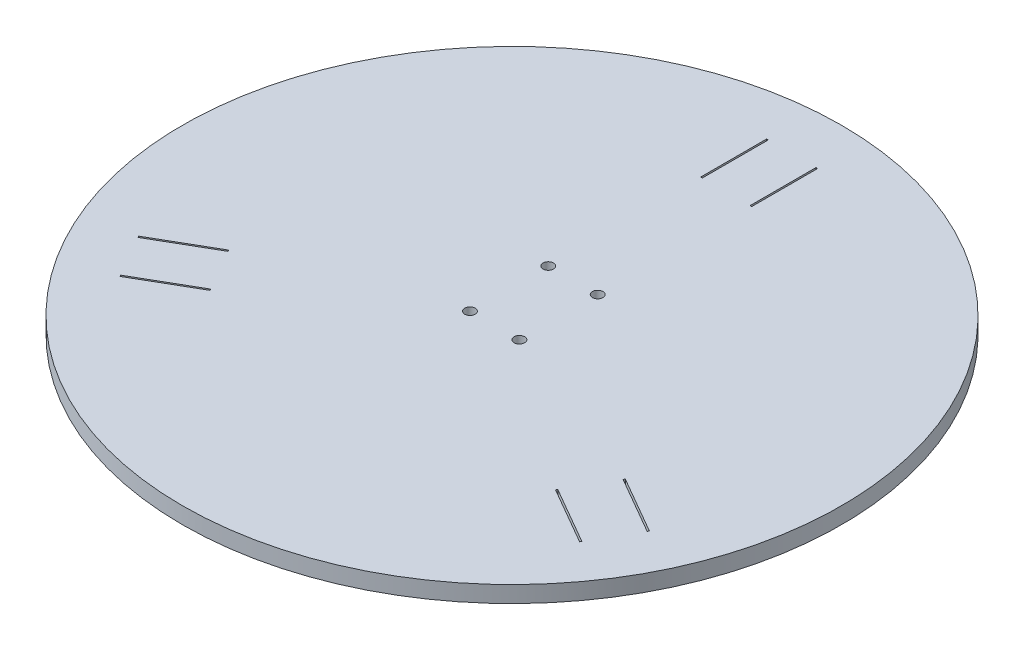
SolidWorks part; units mm, degrees
ref_plane "Front Plane" through (0, 0, 0) normal (0, 0, 1) x (1, 0, 0)
ref_plane "Top Plane" through (0, 0, 0) normal (0, 1, 0) x (1, 0, 0)
ref_plane "Right Plane" through (0, 0, 0) normal (1, 0, 0) x (0, 0, -1)
sketch "Sketch2" plane through (0, 0, 0) normal (0, 1, 0) x (1, 0, 0)
  circle A0 centre (0, 0) radius 100
  dimension "D1" = 200
extrude "Boss-Extrude1" add sketch "Sketch2" along normal blind 5
sketch "Sketch3" plane through (0, 5, 0) normal (0, 1, 0) x (1, 0, 0)
  line L0 (0, 0) -> (0, 100) construction
  line L1 (-7.5, 75) -> (7.5, 75) construction
  line L3 (-7.75, 65) -> (-7.25, 65)
  line L4 (-7.75, 65) -> (-7.75, 85)
  line L5 (-7.75, 85) -> (-7.25, 85)
  line L6 (-7.25, 65) -> (-7.25, 85)
  line L7 (-7.75, 65) -> (-7.25, 85) construction
  line L8 (-7.75, 85) -> (-7.25, 65) construction
  line L9 (7.25, 65) -> (7.75, 65)
  line L10 (7.25, 65) -> (7.25, 85)
  line L11 (7.25, 85) -> (7.75, 85)
  line L12 (7.75, 65) -> (7.75, 85)
  line L13 (7.25, 65) -> (7.75, 85) construction
  line L14 (7.25, 85) -> (7.75, 65) construction
  line L30 (60.1667, -25.7883) -> (77.4872, -35.7883)
  line L31 (60.1667, -25.7883) -> (59.9167, -26.2213)
  line L32 (59.9167, -26.2213) -> (77.2372, -36.2213)
  line L33 (77.4872, -35.7883) -> (77.2372, -36.2213)
  line L34 (52.6667, -38.7787) -> (69.9872, -48.7787)
  line L35 (52.6667, -38.7787) -> (52.4167, -39.2117)
  line L36 (52.4167, -39.2117) -> (69.7372, -49.2117)
  line L37 (69.9872, -48.7787) -> (69.7372, -49.2117)
  line L38 (-52.4167, -39.2117) -> (-69.7372, -49.2117)
  line L39 (-52.4167, -39.2117) -> (-52.6667, -38.7787)
  line L40 (-52.6667, -38.7787) -> (-69.9872, -48.7787)
  line L41 (-69.7372, -49.2117) -> (-69.9872, -48.7787)
  line L42 (-59.9167, -26.2213) -> (-77.2372, -36.2213)
  line L43 (-59.9167, -26.2213) -> (-60.1667, -25.7883)
  line L44 (-60.1667, -25.7883) -> (-77.4872, -35.7883)
  line L45 (-77.2372, -36.2213) -> (-77.4872, -35.7883)
  circle A0 centre (0, 0) radius 100 construction
  point P8 (0, 75)
  point P34 (0, 0)
  point P36 (0, 0)
  dimension "D1" = 15
  dimension "D2" = 20
  dimension "D3" = 0.5
  dimension "D4" = 75
  dimension "D5" = 3
extrude "Cut-Extrude1" cut sketch "Sketch3" against normal through all
sketch "Sketch6" plane through (0, 0, 0) normal (0, -1, 0) x (-1, 0, 0)
  line L0 (0, 0) -> (0, 50000) construction
  line L1 (0, 0) -> (50000, 0) construction
  point P0 (-7.5, 18.5)
  point P2 (7.5, 18.5)
  point P4 (7.5, -5.25)
  point P6 (-7.5, -5.25)
  point P19 (0, 0)
  dimension "D1" = 15
  dimension "D2" = 18.5
  dimension "D3" = 23.75
hole_wizard "Ø3.2 (3.2) Diameter Hole1" positions "Sketch6" profile "Sketch5" hole size "Ø3.2" standard "ANSI Metric" end condition through all
sketch "Sketch5" plane through (7.5, 0, -18.5) normal (1, 0, 0) x (0, 0, -1)
  line L0 (0, 0) -> (0, 5)
  line L1 (0, 5) -> (1.6, 5)
  line L2 (1.6, 5) -> (1.6, 0.025)
  line L3 (1.6, 0.025) -> (1.625, 0)
  line L5 (1.625, 0) -> (0, 0)
  line L6 (-1.6, 0.025) -> (-1.625, 0) construction
  line L11 (0, -6.35) -> (0, 107.95) construction
  dimension "Thru Hole Dia." = 3.2
  dimension "Thru Hole Depth" = 5
  dimension "Near C'Sink Dia." = 3.25
  dimension "Near C'Sink Angle" = 90
equation "\"Leg_Spacing\"=40"
equation "\"Leaf_Spring_Slot_Width\"=5"
equation "\"Leaf_Spring_Thickness\"=0.2"
equation "\"Inner_Radius\"=75"
equation "\"Camera\"=120"
